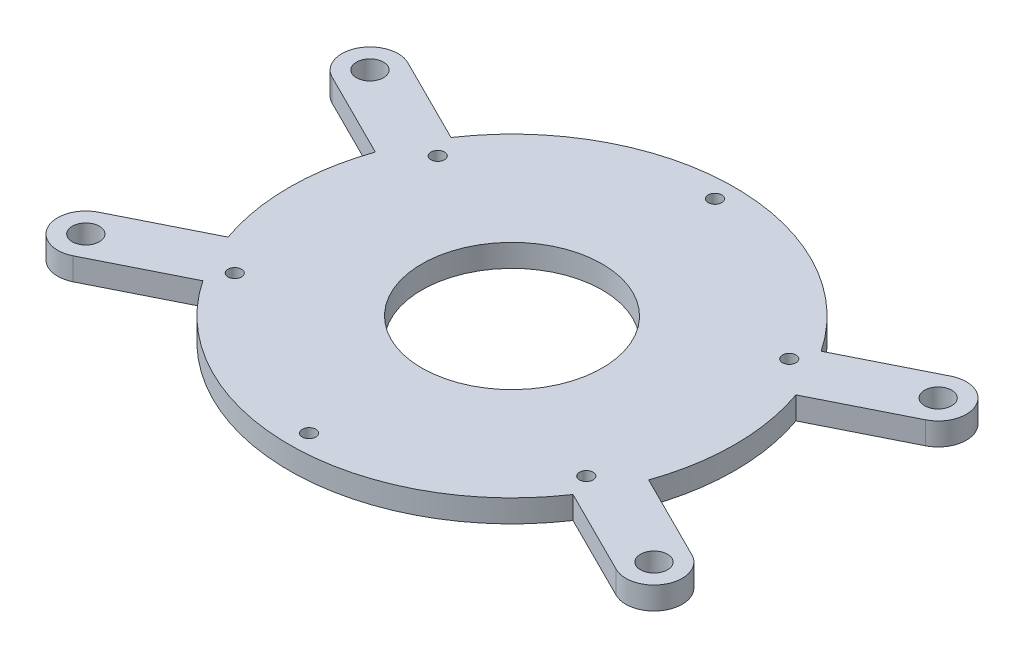
SolidWorks part; units mm, degrees
ref_plane "前视基准面" through (0, 0, 0) normal (0, 0, 1) x (1, 0, 0)
ref_plane "上视基准面" through (0, 0, 0) normal (0, 1, 0) x (1, 0, 0)
ref_plane "右视基准面" through (0, 0, 0) normal (1, 0, 0) x (0, 0, -1)
sketch "草图1" plane through (0, 0, 0) normal (0, 1, 0) x (1, 0, 0)
  line L0 (65.782, 25.9101) -> (46.6233, 16.3287)
  line L1 (60.1908, 37.0899) -> (41.0322, 27.5085)
  line L2 (0, 135.0816) -> (0, -134.5462) construction
  line L3 (161.8892, 80.9621) -> (-87.1466, -43.5827) construction
  line L7 (-65.782, 25.9101) -> (-46.6233, 16.3287)
  line L8 (-50, 21.5) -> (50, 21.5) construction
  line L9 (-50, 21.5) -> (-50, -21.5) construction
  line L10 (-50, -21.5) -> (50, -21.5) construction
  line L11 (50, 21.5) -> (50, -21.5) construction
  line L12 (-60.1908, 37.0899) -> (-41.0322, 27.5085)
  line L13 (-133.256, 0) -> (145.6129, 0) construction
  line L14 (65.782, -25.9101) -> (46.6233, -16.3287)
  line L15 (60.1908, -37.0899) -> (41.0322, -27.5085)
  line L16 (-65.782, -25.9101) -> (-46.6233, -16.3287)
  line L17 (-60.1908, -37.0899) -> (-41.0322, -27.5085)
  circle A0 centre (0, 0) radius 20
  circle A1 centre (0, 0) radius 49.4
  circle A2 centre (62.9864, 31.5) radius 6.25
  circle A6 centre (-62.9864, 31.5) radius 6.25
  circle A7 centre (62.9864, -31.5) radius 6.25
  circle A8 centre (-62.9864, -31.5) radius 6.25
  point P19 (0, 21.5)
  point P20 (50, 0)
  point P41 (0, 0)
  dimension "D2" = 12.5
  dimension "D5" = 98.8
  dimension "D7" = 40
  dimension "D1" = 63.43
  dimension "D3" = 100
  dimension "D4" = 43
  dimension "D6" = 10
extrude "凸台-拉伸1" add sketch "草图1" along normal blind 5 contours A1 A0 | L12 A6 L7 A1 | A8 L17 A1 L16 | A8 | L15 A7 L14 A1 | A7 | A2 | A2 L1 A1 L0 | A6 region at (51.3835, 0, -25.6973) region at (62.9864, 0, -31.5) region at (47.3234, 0, -8.0473) region at (51.3835, 0, 25.6973) region at (-51.3835, 0, -25.6973) region at (62.9864, 0, 31.5) region at (-51.3835, 0, 25.6973) region at (-62.9864, 0, 31.5)
sketch "草图2" plane through (0, 5, 0) normal (0, 1, 0) x (1, 0, 0)
  line L0 (0, 78.1952) -> (0, -57.2274) construction
  line L1 (-93.9988, 0) -> (82.0699, 0) construction
  circle A0 centre (-62.9864, 31.5) radius 3
  arc A1 (-60.1908, 37.0899) -> (-65.782, 25.9101) centre (-62.9864, 31.5) ccw construction
  dimension "D1" = 6
extrude "切除-拉伸1" cut sketch "草图2" against normal up to next
mirror "镜向1" about plane through (0, 0, 0) normal (0, 0, 1) of "切除-拉伸1"
mirror "镜向2" about plane through (0, 0, 0) normal (1, 0, 0) of "镜向1"
sketch "草图3" plane through (0, 0, 0) normal (0, -1, 0) x (1, 0, 0)
  circle A0 centre (0, 45) radius 1.5
  dimension "D1" = 3
  dimension "D2" = 45
extrude "切除-拉伸2" cut sketch "草图3" against normal through all
cosmetic thread "装饰螺纹线1" parameters "D2"=4
pattern_circular "阵列(圆周)1" count 6 over 360 about axis through (0, 0, 0) along (0, 1, 0) of "切除-拉伸2"
cosmetic thread "装饰螺纹线2" parameters "D2"=4
cosmetic thread "装饰螺纹线3" parameters "D2"=4
cosmetic thread "装饰螺纹线4" parameters "D2"=4
cosmetic thread "装饰螺纹线5" parameters "D2"=4
cosmetic thread "装饰螺纹线6" parameters "D2"=4
